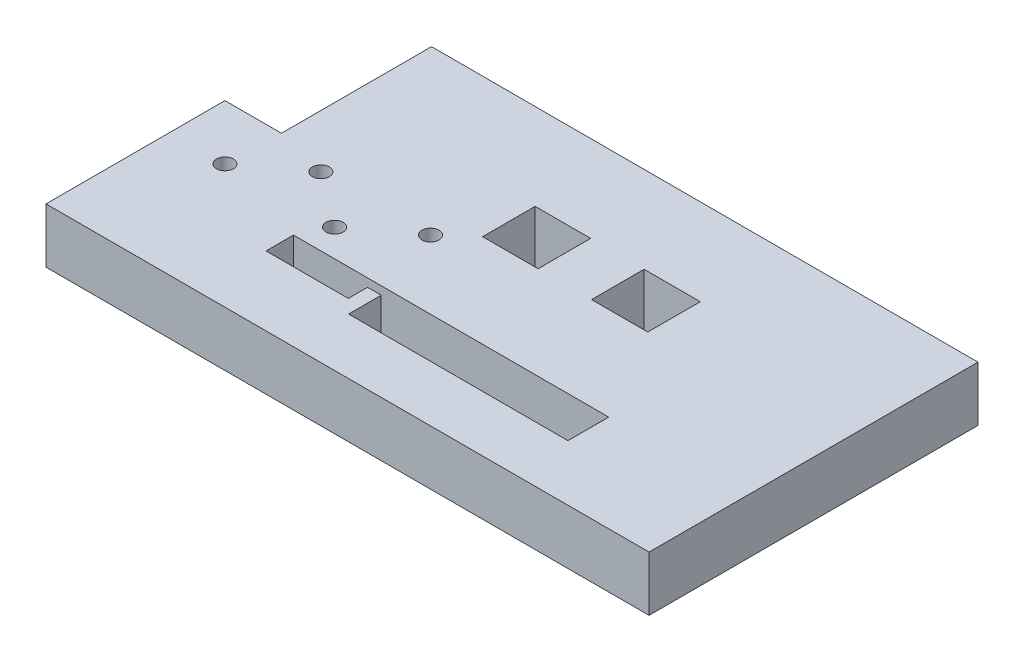
SolidWorks part; units mm, degrees
material "Plain Carbon Steel"
ref_plane "Front Plane" through (0, 0, 0) normal (0, 0, 1) x (1, 0, 0)
ref_plane "Top Plane" through (0, 0, 0) normal (0, 1, 0) x (1, 0, 0)
ref_plane "Right Plane" through (0, 0, 0) normal (1, 0, 0) x (0, 0, -1)
sketch "Sketch1" plane through (0, 0, 0) normal (0, 1, 0) x (1, 0, 0)
  line L1 (-110, -60) -> (110, -60)
  line L2 (-110, -60) -> (-110, 60)
  line L3 (-110, 60) -> (110, 60)
  line L4 (110, -60) -> (110, 60)
  line L5 (-110, -60) -> (110, 60) construction
  line L6 (-110, 60) -> (110, -60) construction
  point P0 (0, 0)
  dimension "D1" = 120
  dimension "D2" = 220
extrude "Boss-Extrude1" add sketch "Sketch1" against normal blind 20
sketch "Sketch2" plane through (0, 0, 0) normal (0, 1, 0) x (1, 0, 0)
  line L1 (-110, 60) -> (-89.3675, 60)
  line L2 (-110, 60) -> (-110, 5.27)
  line L3 (-110, 5.27) -> (-89.3675, 5.27)
  line L4 (-89.3675, 60) -> (-89.3675, 5.27)
  line L5 (-90, -14.72) -> (-89.3675, 5.27) construction
  line L10 (-70, 0.28) -> (-89.3675, 5.27) construction
  circle A0 centre (-90, -14.72) radius 3.1 construction
  circle A1 centre (-70, 0.28) radius 3.1 construction
  point P7 (0, 0)
  point P10 (0, 0)
  dimension "D1" = 20
extrude "Cut-Extrude1" cut sketch "Sketch2" against normal up to next
sketch "Sketch3" plane through (0, 0, 0) normal (0, 1, 0) x (1, 0, 0)
  line L6 (-20, 28.44) -> (-20, 9.28)
  line L7 (-20, 9.28) -> (0.25, 9.28)
  line L8 (0.25, 9.28) -> (0.25, 28.44)
  line L9 (19.75, 28.44) -> (19.75, 9.28)
  line L10 (19.75, 9.28) -> (40.25, 9.28)
  line L11 (40.25, 9.28) -> (40.25, 28.44)
  line L12 (-20, 28.44) -> (0.25, 28.44)
  line L14 (19.75, 28.44) -> (40.25, 28.44)
  line L15 (5.31, 28.5) -> (-15.06, 28.5) construction
  line L18 (40.25, 9.28) -> (40.25, 27.5) construction
  line L19 (19.75, 27.5) -> (19.75, 9.28) construction
  line L20 (19.75, 9.28) -> (40.25, 9.28) construction
  line L21 (0.25, 9.28) -> (0.25, 27.5) construction
  line L22 (-20, 9.28) -> (0.25, 9.28) construction
  line L23 (-20, 27.5) -> (-20, 9.28) construction
  point P10 (0, 0)
  dimension "D1" = 0.06
extrude "Cut-Extrude2" cut sketch "Sketch3" against normal up to next
sketch "Sketch4" plane through (0, 0, 0) normal (0, 1, 0) x (1, 0, 0)
  line L0 (-15.06, -39.66) -> (65.06, -39.66) construction
  line L1 (60, -24.72) -> (-20, -24.72)
  line L2 (60, -24.72) -> (60, -39.6)
  line L3 (60, -39.6) -> (-20, -39.6)
  line L4 (-20, -24.72) -> (-20, -39.6)
  point P7 (0, 0)
  dimension "D1" = 80
  dimension "D2" = 0.06
  dimension "D3" = 14.88
extrude "Cut-Extrude3" cut sketch "Sketch4" against normal up to next
sketch "Sketch8" plane through (0, 0, 0) normal (0, 1, 0) x (1, 0, 0)
  circle A0 centre (-70, 0.28) radius 3.1 construction
  circle A1 centre (-90, -14.72) radius 3.1
  circle A2 centre (-90, -14.72) radius 3.1
  circle A3 centre (-30, 0.28) radius 3.1
  circle A4 centre (-30, 0.28) radius 3.1
  circle A5 centre (-70, 0.28) radius 3.1
  circle A6 centre (-50, -14.72) radius 3.1 construction
  circle A7 centre (-50, -14.72) radius 3.1
  dimension "D1" = 0
  dimension "D2" = 0
extrude "Cut-Extrude4" cut sketch "Sketch8" against normal up to next
sketch "Sketch9" plane through (0, 0, 0) normal (0, 1, 0) x (1, 0, 0)
  line L0 (-20, -27.72) -> (-25, -27.72)
  line L1 (-20, -24.72) -> (-55, -24.72)
  line L2 (-20, -24.72) -> (-20, -27.72)
  line L3 (-25, -34.72) -> (-55, -34.72)
  line L4 (-55, -24.72) -> (-55, -34.72)
  line L5 (-25, -27.72) -> (-25, -34.72)
  dimension "D1" = 10
  dimension "D2" = 5
  dimension "D3" = 30
  dimension "D4" = 3
extrude "Cut-Extrude5" cut sketch "Sketch9" against normal up to next
